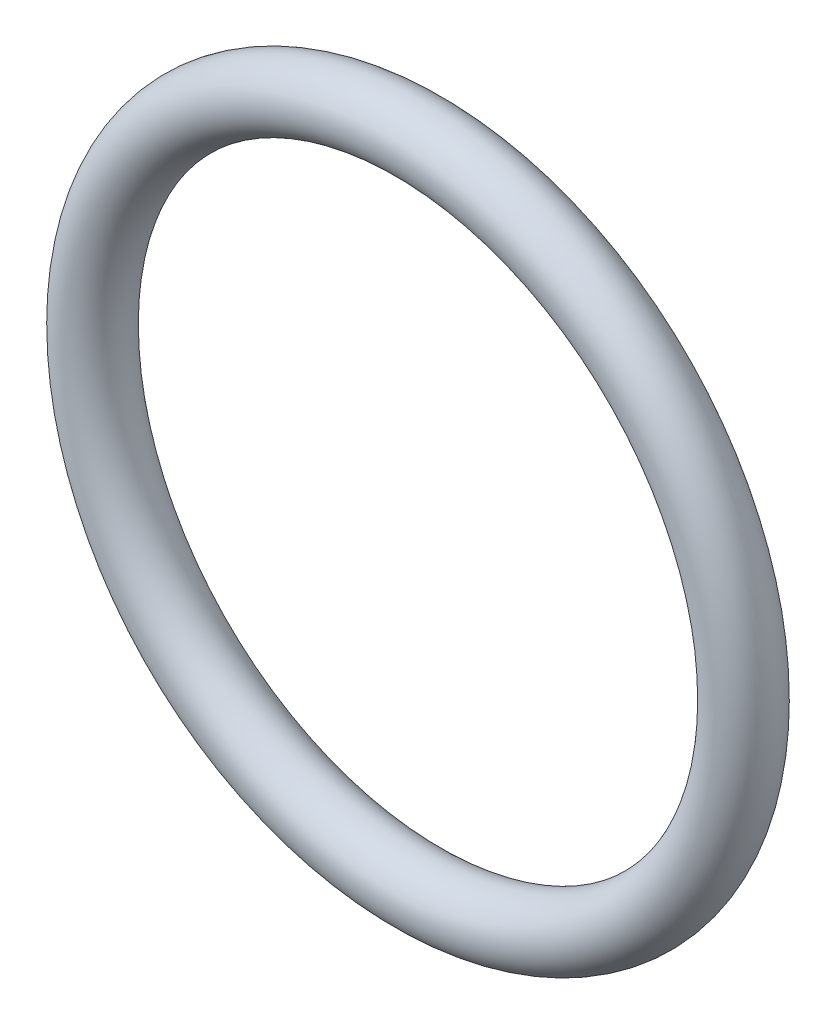
SolidWorks part; units mm, degrees
ref_plane "Front" through (0, 0, 0) normal (0, 0, 1) x (1, 0, 0)
ref_plane "Top" through (0, 0, 0) normal (0, 1, 0) x (1, 0, 0)
ref_plane "Right" through (0, 0, 0) normal (1, 0, 0) x (0, 0, -1)
sketch "Sketch1" plane through (0, 0, 0) normal (0, 0, 1) x (1, 0, 0)
  circle A0 centre (0, 0) radius 10.85
  dimension "d1" = 21.7
sketch "Sketch2" plane through (0, 0, 0) normal (0, 1, 0) x (1, 0, 0)
  circle A0 centre (-12.05, 0) radius 1.2
  point P2 (-10.85, 0)
  dimension "d2" = 2.4
sweep "Sweep1" add profiles "Sketch2" path "Sketch1"
ref_axis "Axis1" through (0, 0, -5.0798) along (0, 0, 1)
